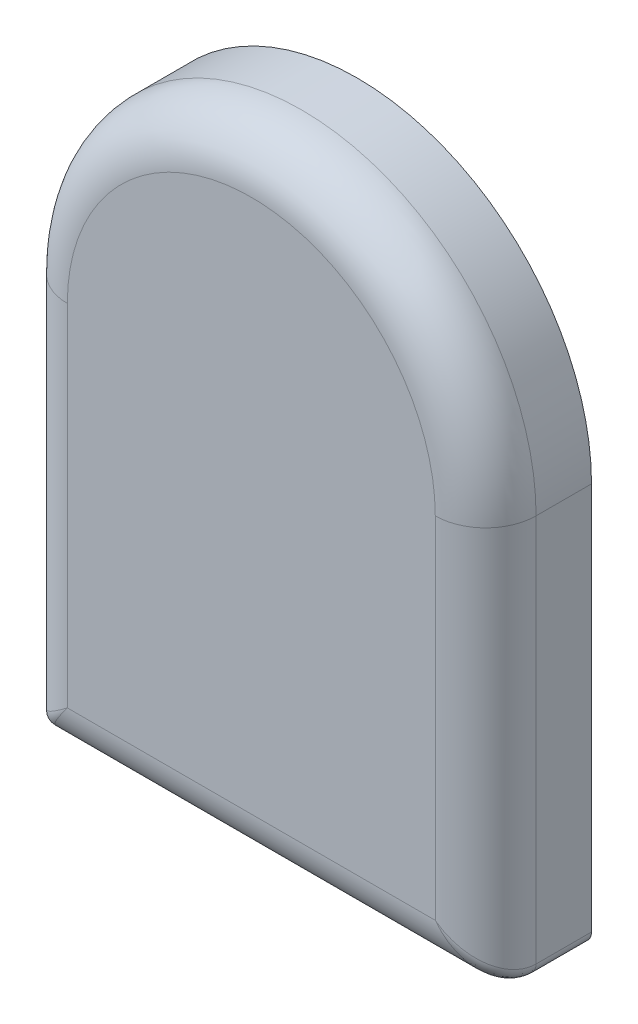
SolidWorks part; units mm, degrees
ref_plane "前视基准面" through (0, 0, 0) normal (0, 0, 1) x (1, 0, 0)
ref_plane "上视基准面" through (0, 0, 0) normal (0, 1, 0) x (1, 0, 0)
ref_plane "右视基准面" through (0, 0, 0) normal (1, 0, 0) x (0, 0, -1)
other "Configuration Table"
sketch "草图1" plane through (0, 0, 0) normal (0, 0, 1) x (1, 0, 0)
  line L0 (8.8, -12.6) -> (-8.8, -12.6)
  line L1 (-9.3, -12.1) -> (-9.3, 3.3)
  line L2 (9.3, 3.3) -> (9.3, -12.1)
  arc A0 (8.8, -12.6) -> (9.3, -12.1) centre (8.8, -12.1) ccw
  arc A1 (-9.3, -12.1) -> (-8.8, -12.6) centre (-8.8, -12.1) ccw
  arc A2 (9.3, 3.3) -> (-9.3, 3.3) centre (0, 3.3) ccw
extrude "凸台-拉伸1" add sketch "草图1" along normal blind 4.2
fillet "圆角1" radius 2 6 edges at (9.1536, -12.4536, 4.2) (9.3, -4.4, 4.2) (0, 12.6, 4.2) (-9.3, -4.4, 4.2) (-9.1536, -12.4536, 4.2) (0, -12.6, 4.2)
